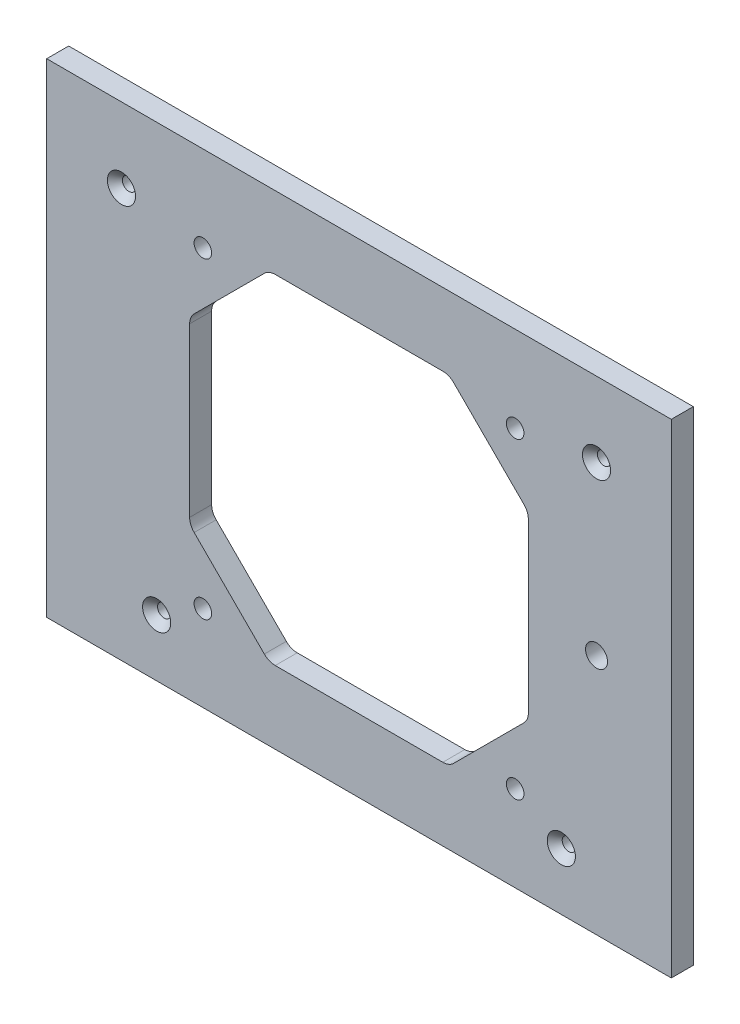
SolidWorks part; units mm, degrees
ref_plane "Front Plane" through (0, 0, 0) normal (0, 0, 1) x (1, 0, 0)
ref_plane "Top Plane" through (0, 0, 0) normal (0, 1, 0) x (1, 0, 0)
ref_plane "Right Plane" through (0, 0, 0) normal (1, 0, 0) x (0, 0, -1)
sketch "Sketch1" plane through (0, 0, 0) normal (0, 0, 1) x (1, 0, 0)
  line L1 (71, -55) -> (-71, -55)
  line L2 (71, -55) -> (71, 55)
  line L3 (71, 55) -> (-71, 55)
  line L4 (-71, -55) -> (-71, 55)
  line L5 (71, -55) -> (-71, 55) construction
  line L6 (71, 55) -> (-71, -55) construction
  point P0 (0, 0)
  dimension "D1" = 142
  dimension "D2" = 110
extrude "Boss-Extrude1" add sketch "Sketch1" along normal mid plane 5
sketch "Sketch3" plane through (0, 0, 2.5) normal (0, 0, 1) x (1, 0, 0)
  line L0 (71, -55) -> (71, 55) construction
  line L1 (71, 55) -> (-71, 55) construction
  line L2 (-71, 55) -> (-71, -55) construction
  circle A0 centre (-54, 38) radius 1.5
  circle A1 centre (54, 38) radius 1.5
  dimension "D3" = 3
  dimension "D1" = 17
  dimension "D2" = 17
  dimension "D4" = 17
extrude "TopCoverHoles" cut sketch "Sketch3" against normal through all
sketch "Sketch5" plane through (0, 0, 2.5) normal (0, 0, 1) x (1, 0, 0)
  line L0 (-71, 55) -> (-71, -55) construction
  line L1 (71, -55) -> (71, 55) construction
  line L2 (-71, -55) -> (71, -55) construction
  circle A0 centre (46, -42) radius 1.5
  circle A1 centre (-46, -42) radius 1.5
  dimension "D3" = 3
  dimension "D1" = 25
  dimension "D2" = 25
  dimension "D4" = 13
extrude "Cut-Extrude1" cut sketch "Sketch5" against normal through all
chamfer "Chamfer1" distance 1.7 angle 45 4 edges at (55.5, 38, 2.5) (-52.5, 38, 2.5) (47.5, -42, 2.5) (-44.5, -42, 2.5)
sketch "Sketch7" plane through (0, 0, 2.5) normal (0, 0, 1) x (1, 0, 0)
  line L0 (-20.5, 38.5) -> (-38.5, 20.5)
  line L1 (20.5, -38.5) -> (-20.5, -38.5)
  line L2 (38.5, -20.5) -> (38.5, 20.5)
  line L3 (20.5, 38.5) -> (-20.5, 38.5)
  line L4 (-38.5, -20.5) -> (-38.5, 20.5)
  line L5 (38.5, -38.5) -> (-38.5, 38.5) construction
  line L6 (38.5, 38.5) -> (-38.5, -38.5) construction
  line L7 (-20.5, -38.5) -> (-38.5, -20.5)
  line L8 (38.5, -20.5) -> (20.5, -38.5)
  line L9 (38.5, 20.5) -> (20.5, 38.5)
  circle A0 centre (0, 0) radius 38.5 construction
  circle A1 centre (-35.5, -35.5) radius 2
  circle A2 centre (35.5, -35.5) radius 2
  circle A3 centre (35.5, 35.5) radius 2
  circle A4 centre (-35.5, 35.5) radius 2
  dimension "D3" = 4
  dimension "D10" = 77
  dimension "D4" = 71
  dimension "D5" = 71
  dimension "D11" = 77
extrude "Fan" cut sketch "Sketch7" against normal through all
chamfer "FanChamfer" [suppressed] distance 3 angle 45
sketch "Sketch8" plane through (0, 0, 2.5) normal (0, 0, 1) x (1, 0, 0)
  line L2 (71, -55) -> (71, 55) construction
  circle A0 centre (54, 0) radius 2.5
  dimension "D1" = 17
  dimension "D2" = 5
extrude "ForLED" cut sketch "Sketch8" against normal through all
fillet "Fillet1" radius 3.5 8 edges at (38.5, 20.5, 0) (38.5, -20.5, 0) (20.5, -38.5, 0) (-38.5, -20.5, 0) (-38.5, 20.5, 0) (-20.5, 38.5, 0) (20.5, 38.5, 0) (-20.5, -38.5, 0)
